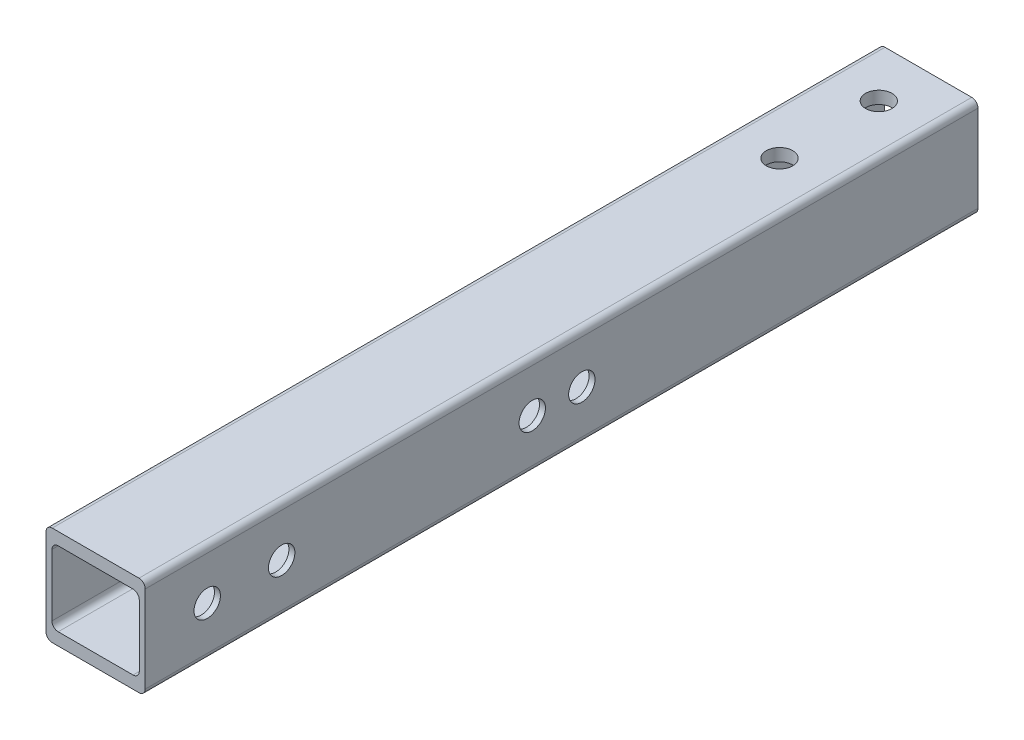
SolidWorks part; units mm, degrees
note: '?' marks a value the reader was unsure of.
ref_plane "Front Plane" through (0, 0, 0) normal (0, 0, 1) x (1, 0, 0)
ref_plane "Top Plane" through (0, 0, 0) normal (0, 1, 0) x (1, 0, 0)
ref_plane "Right Plane" through (0, 0, 0) normal (1, 0, 0) x (0, 0, -1)
sketch "Sketch1" plane through (0, 0, 0) normal (0, 0, 1) x (1, 0, 0)
  line L0 (12.7, 0) -> (9.525, 0) construction
  line L1 (-12.7, 0) -> (12.7, 0) construction
  line L2 (0, 12.7) -> (0, -12.7)
  point P7 (0, 0)
sketch "Sketch2" plane through (0, 0, 0) normal (1, 0, 0) x (0, 0, -1)
  line L0 (914.4, 0) -> (-914.4, 0)
  point P4 (0, 0)
  dimension "Length" = 1828.8
sketch "Sketch3" plane through (0, 0, 0) normal (0, 0, 1) x (1, 0, 0)
  line L5 (-11.176, -9.525) -> (11.176, -9.525)
  line L6 (-11.176, -9.525) -> (-11.176, 9.525)
  line L11 (-11.176, 9.525) -> (11.176, 9.525)
  line L12 (11.176, -9.525) -> (11.176, 9.525)
  line L14 (-11.176, -9.525) -> (11.176, 9.525) construction
  line L15 (-11.176, 9.525) -> (11.176, -9.525) construction
  line L16 (-12.7, -12.7) -> (12.7, -12.7)
  line L17 (-12.7, -12.7) -> (-12.7, 12.7)
  line L18 (-12.7, 12.7) -> (12.7, 12.7)
  line L19 (12.7, -12.7) -> (12.7, 12.7)
  line L20 (-12.7, -12.7) -> (12.7, 12.7) construction
  line L21 (-12.7, 12.7) -> (12.7, -12.7) construction
  point P0 (0, 0)
  point P5 (0, 0)
  point P10 (11.176, -12.7)
  dimension "D1" = 1.524
extrude "Boss-Extrude1" add sketch "Sketch3" along normal mid plane 136.9619
fillet "Fillet1" radius 1.6002 8 edges at (-11.176, -9.525, 0) (11.176, -9.525, 0) (-11.176, 9.525, 0) (11.176, 9.525, 0) (-12.7, -12.7, 0) (12.7, -12.7, 0) (-12.7, 12.7, 0) (12.7, 12.7, 0)
sketch "Sketch4" plane through (0, 0, 0) normal (1, 0, 0) x (0, 0, -1)
  line L0 (68.4809, 0) -> (-68.4809, 0) construction
  line L1 (-68.4809, -11.0998) -> (-68.4809, 11.0998) construction
  line L2 (68.4809, -11.0998) -> (68.4809, 11.0998) construction
  point P0 (-39.9059, 0)
  point P6 (0, 0)
  point P8 (-30.3809, 0)
  point P9 (30.3809, 0)
  point P10 (39.9059, 0)
  dimension "D1" = 28.575
  dimension "D2" = 38.1
  dimension "D3" = 28.575
  dimension "D4" = 38.1
sketch "Sketch5" plane through (-12.7, 0, 0) normal (-1, 0, 0) x (0, 0, 1)
  line L0 (-68.4809, 12.7) -> (-24.4868, -12.7)
  line L1 (68.4809, -12.7) -> (-68.4809, -12.7) construction
  line L2 (-24.4868, -12.7) -> (-68.4809, -12.7)
  line L3 (-68.4809, -12.7) -> (-68.4809, 12.7)
  dimension "D1" = 30
extrude "Cut-Extrude1" [suppressed] cut sketch "Sketch5" against normal through all
mirror "Mirror1" [suppressed] about plane through (0, 0, 0) normal (0, 0, 1)
ref_axis "Axis1" through (-9.525, -0.6172, 55.7809) along (-1, 0, 0)?
ref_plane "Plane1" through (0, -0.6172, 0) normal (0, 1, 0) x (1, 0, 0)
ref_plane "Plane2" [suppressed] through (0, -17.0101, 9.8208) normal (0, -0.866, 0.5) x (-1, 0, 0)
hole_wizard "1/4 Clearance Hole1" [suppressed] positions "Sketch8" profile "Sketch9" hole size "1/4" standard "ANSI Inch"
sketch "Sketch8" [suppressed] plane through (-9.525, 0, 0) normal (-1, 0, 0) x (0, 0, 1)
  line L1 (0.747, -22.2489) -> (18.8946, -11.7714) construction
  point P0 (39.2832, 0)
sketch "Sketch9" plane through (-9.525, 0, 39.2832) normal (0, 1, 0) x (0, 0, 1)
  line L0 (0, 0) -> (0, 19.05)
  line L1 (0, 19.05) -> (3.3782, 19.05)
  line L2 (3.3782, 19.05) -> (3.3782, 0)
  line L5 (3.3782, 0) -> (0, 0)
  line L11 (0, -6.35) -> (0, 107.95) construction
  dimension "Thru Hole Dia." = 6.7564
  dimension "Thru Hole Depth" = 19.05
sketch "Sketch10" plane through (-12.7, 0, 0) normal (-1, 0, 0) x (0, 0, 1)
  circle A0 centre (-23.328, 0) radius 3.3782 construction
  circle A1 centre (-76.668, 0) radius 3.3782 construction
  circle A2 centre (-23.328, 0) radius 3.3782
  circle A3 centre (-76.668, 0) radius 3.3782
extrude "Cut-Extrude2" [suppressed] cut sketch "Sketch10" against normal up to surface (25.4 mm away)
hole_wizard "1/4 Clearance Hole2" positions "Sketch12" profile "Sketch13" hole size "1/4" standard "ANSI Inch" end condition through all
sketch "Sketch12" plane through (-12.7, 0, 0) normal (-1, 0, 0) x (0, 0, 1)
  line L0 (68.4809, 11.0998) -> (68.4809, -11.0998) construction
  point P0 (32.9209, 0)
  point P2 (45.6209, 0)
  dimension "D1" = 12.7
  dimension "D2" = 22.86
sketch "Sketch13" plane through (-12.7, 0, 32.9209) normal (0, 1, 0) x (0, 0, 1)
  line L0 (0, 0) -> (0, 25.4)
  line L1 (0, 25.4) -> (3.3782, 25.4)
  line L2 (3.3782, 25.4) -> (3.3782, 0)
  line L5 (3.3782, 0) -> (0, 0)
  line L11 (0, -6.35) -> (0, 107.95) construction
  dimension "Thru Hole Dia." = 6.7564
  dimension "Thru Hole Depth" = 25.4
hole_wizard "1/4 Clearance Hole3" positions "Sketch14" profile "Sketch15" hole size "1/4" standard "ANSI Inch" end condition through all
sketch "Sketch14" plane through (0, 12.7, 0) normal (0, 1, 0) x (1, 0, 0)
  line L1 (11.0998, 68.4809) -> (-11.0998, 68.4809) construction
  point P0 (0, 55.7809)
  point P2 (0, 30.3809)
  dimension "D1" = 12.7
  dimension "D2" = 25.4
sketch "Sketch15" plane through (0, 12.7, -55.7809) normal (1, 0, 0) x (0, 0, 1)
  line L0 (0, 0) -> (0, 25.4)
  line L1 (0, 25.4) -> (3.3782, 25.4)
  line L2 (3.3782, 25.4) -> (3.3782, 0)
  line L5 (3.3782, 0) -> (0, 0)
  line L11 (0, -6.35) -> (0, 107.95) construction
  dimension "Thru Hole Dia." = 6.7564
  dimension "Thru Hole Depth" = 25.4
sketch "Sketch16" plane through (0, 0, 68.4809) normal (0, 0, 1) x (1, 0, 0)
  line L4 (-12.7, 11.0998) -> (-12.7, -11.0998)
  line L5 (-11.0998, -12.7) -> (11.0998, -12.7)
  line L6 (12.7, -11.0998) -> (12.7, 11.0998)
  line L7 (11.0998, 12.7) -> (-11.0998, 12.7)
  line L8 (-12.7, 11.0998) -> (-12.7, -11.0998)
  line L9 (-11.0998, -12.7) -> (11.0998, -12.7)
  line L10 (12.7, -11.0998) -> (12.7, 11.0998)
  line L11 (11.0998, 12.7) -> (-11.0998, 12.7)
  line L12 (11.176, -7.9248) -> (11.176, 7.9248)
  line L13 (-9.5758, -9.525) -> (9.5758, -9.525)
  line L14 (-11.176, 7.9248) -> (-11.176, -7.9248)
  line L15 (9.5758, 9.525) -> (-9.5758, 9.525)
  line L16 (11.176, -7.9248) -> (11.176, 7.9248)
  line L17 (-9.5758, -9.525) -> (9.5758, -9.525)
  line L18 (-11.176, 7.9248) -> (-11.176, -7.9248)
  line L19 (9.5758, 9.525) -> (-9.5758, 9.525)
  arc A4 (-12.7, -11.0998) -> (-11.0998, -12.7) centre (-11.0998, -11.0998) ccw
  arc A5 (11.0998, -12.7) -> (12.7, -11.0998) centre (11.0998, -11.0998) ccw
  arc A6 (12.7, 11.0998) -> (11.0998, 12.7) centre (11.0998, 11.0998) ccw
  arc A7 (-11.0998, 12.7) -> (-12.7, 11.0998) centre (-11.0998, 11.0998) ccw
  arc A8 (-12.7, -11.0998) -> (-11.0998, -12.7) centre (-11.0998, -11.0998) ccw
  arc A9 (11.0998, -12.7) -> (12.7, -11.0998) centre (11.0998, -11.0998) ccw
  arc A10 (12.7, 11.0998) -> (11.0998, 12.7) centre (11.0998, 11.0998) ccw
  arc A11 (-11.0998, 12.7) -> (-12.7, 11.0998) centre (-11.0998, 11.0998) ccw
  arc A12 (9.5758, -9.525) -> (11.176, -7.9248) centre (9.5758, -7.9248) ccw
  arc A13 (-11.176, -7.9248) -> (-9.5758, -9.525) centre (-9.5758, -7.9248) ccw
  arc A14 (-9.5758, 9.525) -> (-11.176, 7.9248) centre (-9.5758, 7.9248) ccw
  arc A15 (11.176, 7.9248) -> (9.5758, 9.525) centre (9.5758, 7.9248) ccw
  arc A16 (9.5758, -9.525) -> (11.176, -7.9248) centre (9.5758, -7.9248) ccw
  arc A17 (-11.176, -7.9248) -> (-9.5758, -9.525) centre (-9.5758, -7.9248) ccw
  arc A18 (-9.5758, 9.525) -> (-11.176, 7.9248) centre (-9.5758, 7.9248) ccw
  arc A19 (11.176, 7.9248) -> (9.5758, 9.525) centre (9.5758, 7.9248) ccw
  dimension "D1" = 0
  dimension "D2" = 0
extrude "Boss-Extrude2" add sketch "Sketch16" along normal blind 76.2
sketch "Sketch17" plane through (12.7, 0, 0) normal (1, 0, 0) x (0, 0, -1)
  circle A0 centre (-109.7559, 0) radius 3.3782 construction
  circle A1 centre (-128.8059, 0) radius 3.3782 construction
  circle A3 centre (-109.7559, 0) radius 3.3782
  circle A5 centre (-128.8059, 0) radius 3.3782
extrude "Cut-Extrude3" cut sketch "Sketch17" against normal through all
equation "\"D2@Sketch3\"=\"Wall Thickness@Sketch1\""
equation "\"D1@Sketch4\"=\"Width@Sketch1\"*1.125"
equation "\"D2@Sketch4\"=\"Width@Sketch1\"*1.5"
equation "\"D3@Sketch4\"=\"D1@Sketch4\""
equation "\"D4@Sketch4\"=\"D2@Sketch4\""
